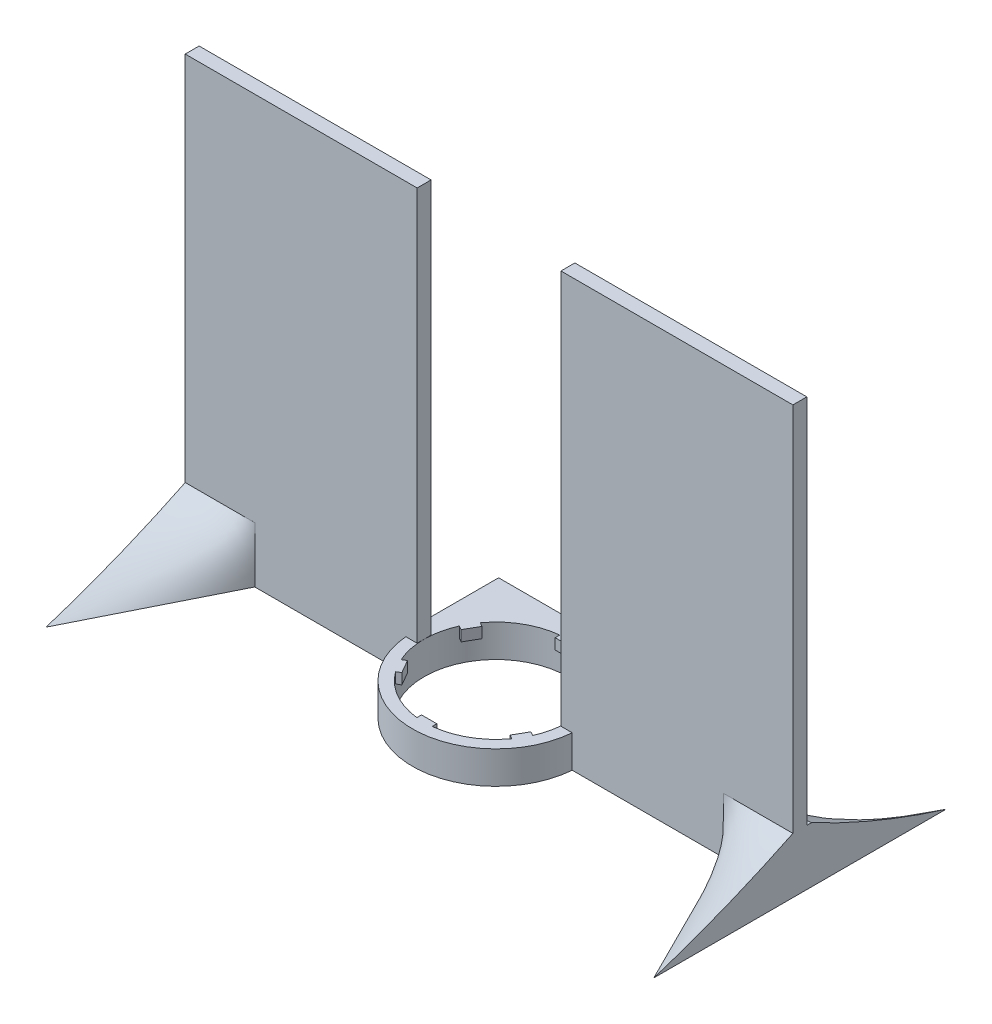
SolidWorks part; units mm, degrees
ref_plane "Front Plane" through (0, 0, 0) normal (0, 0, 1) x (1, 0, 0)
ref_plane "Top Plane" through (0, 0, 0) normal (0, 1, 0) x (1, 0, 0)
ref_plane "Right Plane" through (0, 0, 0) normal (1, 0, 0) x (0, 0, -1)
ref_plane "Plane1" through (15.5, 0, 0) normal (1, 0, 0) x (0, 0, -1)
ref_plane "Plane2" through (120, 0, 0) normal (1, 0, 0) x (0, 0, -1)
sketch "Sketch1" plane through (15.5, 0, 0) normal (1, 0, 0) x (0, 0, -1)
  line L0 (0, 0) -> (0, 12)
  line L1 (0, 55) -> (0, -55) construction
  line L2 (0, 12) -> (0, 92)
  line L3 (0, 92) -> (1.5, 92)
  line L4 (0, 92) -> (-1.5, 92)
  line L6 (1.5, 92) -> (-1.5, 92)
  line L7 (1.5, 92) -> (1.5, 12)
  line L8 (1.5, 12) -> (-1.5, 12)
  line L9 (-1.5, 92) -> (-1.5, 12)
  line L10 (1.5, 12) -> (-1.5, 12)
  line L11 (1.5, 12) -> (1.5, 0)
  line L12 (1.5, 0) -> (-1.5, 0)
  line L13 (-1.5, 12) -> (-1.5, 0)
  point P12 (0, 0)
  dimension "D1" = 80
  dimension "D2" = 3
  dimension "D3" = 12
extrude "Boss-Extrude1" add sketch "Sketch1" along normal blind 50 contours L7 L6 L9 L8
sketch "Sketch5" plane through (65.5, 0, 0) normal (1, 0, 0) x (0, 0, -1)
  line L0 (1.5, 92) -> (1.5, 12) construction
  line L1 (-1.5, 12) -> (2.5, 12)
  line L6 (-31.5, 0) -> (31.5, 0)
  spline S0 degree 2 poles (-1.5, 12) (-16.0718, 4.9063) (-31.5, 0) knots 0 0 0 1 1 1
  spline S1 degree 2 poles (2.5, 12) (16.4462, 4.629) (31.5, 0) knots 0 0 0 1 1 1
  dimension "D2" = 4
  dimension "D3" = 30
  dimension "D1" = 30
sketch "Sketch6" plane through (15.5, 0, 0) normal (-1, 0, 0) x (0, 0, 1)
  line L3 (-1.5, 12) -> (1.5, 12)
  line L4 (-1.5, 12) -> (-1.5, 0)
  line L5 (-1.5, 0) -> (1.5, 0)
  line L6 (1.5, 12) -> (1.5, 0)
  dimension "D1" = 12
ref_plane "Plane3" through (50.5, 0, 0) normal (1, 0, 0) x (0, 0, -1)
sketch "Sketch7" plane through (50.5, 0, 0) normal (1, 0, 0) x (0, 0, -1)
  line L1 (-1.5, 12) -> (1.5, 12)
  line L2 (-1.5, 12) -> (-1.5, 0)
  line L3 (-1.5, 0) -> (1.5, 0)
  line L4 (1.5, 12) -> (1.5, 0)
extrude "Boss-Extrude2" add sketch "Sketch6" against normal up to vertex (35 mm away) contours L6 L5 L4 L3 up to point (50.5, 0, -1.5)
loft "Loft3" add profiles "Sketch7", "Sketch5" connector at (50.5, 0, -1.5) connector at (65.5, 0, -31.5)
mirror "Mirror3" about plane through (0, 0, 0) normal (1, 0, 0) of bodies 105
sketch "Sketch14" plane through (0, 0, 0) normal (0, 1, 0) x (1, 0, 0)
  line L0 (0, -35.2001) -> (0, 35.2001) construction
  circle A0 centre (0, 0) radius 15.5
  circle A1 centre (0, 0) radius 18
  point P4 (0, 14.8838)
  point P11 (0, 0)
  point P12 (0, 0)
  dimension "D1" = 31
  dimension "D2" = 36
extrude "Boss-Extrude3" add sketch "Sketch14" along normal blind 7
sketch "Sketch15" plane through (0, 7, 0) normal (0, 1, 0) x (1, 0, 0)
  line L0 (-1.65, 15.4119) -> (-1.65, 14.4119)
  line L1 (-1.65, 14.4119) -> (1.65, 14.4119)
  line L2 (1.65, 14.4119) -> (1.65, 15.4119)
  line L3 (0, -55) -> (0, 55) construction
  line L4 (-1.65, 15.4119) -> (0, 16.2514)
  line L5 (0, 16.2514) -> (1.65, 15.4119)
  circle A1 centre (0, 0) radius 15.5 construction
  point P12 (0, 14.4119)
  dimension "D1" = 3.3
  dimension "D2" = 1
extrude "Boss-Extrude4" add sketch "Sketch15" against normal blind 2.3
pattern_circular "CirPattern1" count 6 over 360 about axis through (0, 7, 0) along (0, 1, 0) of "Boss-Extrude4"
sketch "Sketch16" plane through (0, 7, 0) normal (0, 1, 0) x (1, 0, 0)
  line L0 (-18.9374, 1.5) -> (-18.9374, 19.5)
  line L1 (-65.5, 1.5) -> (-15.5, 1.5) construction
  line L2 (-18.9374, 19.5) -> (18.9374, 19.5)
  line L3 (18.9374, 19.5) -> (18.9374, 1.5)
  line L4 (65.5, 1.5) -> (15.5, 1.5) construction
  line L5 (18.9374, 1.5) -> (17.9374, 1.5)
  line L6 (-18.9374, 1.5) -> (-17.9374, 1.5)
  line L7 (0, -55) -> (0, 55) construction
  line L8 (15.5, 1.5) -> (17.9374, 1.5) construction
  arc A0 (17.9374, 1.5) -> (-17.9374, 1.5) centre (0, 0) ccw
  point P1 (0, 19.5)
  dimension "D1" = 1
  dimension "D2" = 18
extrude "Boss-Extrude5" add sketch "Sketch16" against normal up to surface (7 mm away) up to face at (0, 0, 15.5)
equation "\"D1@Sketch5\"=\"D3@Sketch5\""
